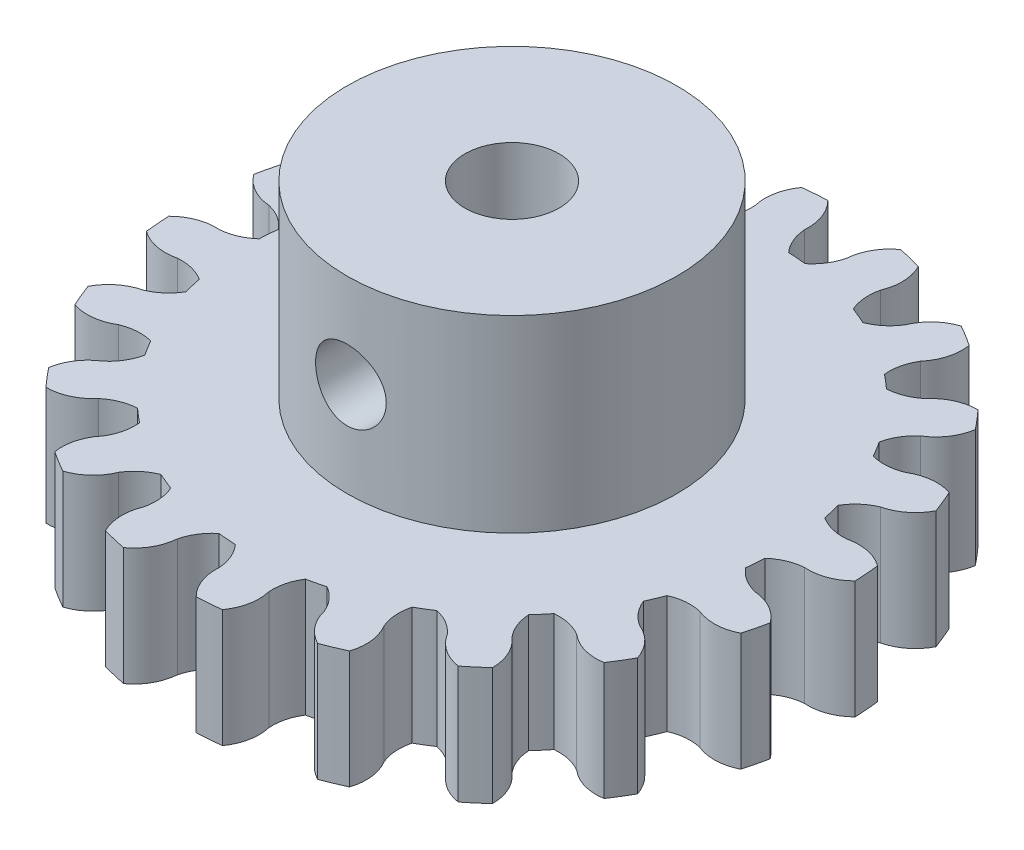
SolidWorks part; units mm, degrees
ref_plane "Front Plane" through (0, 0, 0) normal (0, 0, 1) x (1, 0, 0)
ref_plane "Top Plane" through (0, 0, 0) normal (0, 1, 0) x (1, 0, 0)
ref_plane "Right Plane" through (0, 0, 0) normal (1, 0, 0) x (0, 0, -1)
sketch "Sketch1" plane through (0, 0, 0) normal (0, 1, 0) x (1, 0, 0)
  circle A0 centre (0, 0) radius 14
  circle A1 centre (0, 0) radius 12.73
  circle A2 centre (0, 0) radius 11.25
  circle A3 centre (0, 12.73) radius 2
  circle A4 centre (1.9938, 12.5729) radius 2
  circle A5 centre (-1.9938, 12.5729) radius 2
  circle A6 centre (3.9384, 12.1054) radius 2
  dimension "D1" = 28
  dimension "D2" = 25.46
  dimension "D3" = 22.5
extrude "Boss-Extrude2" add sketch "Sketch1" along normal blind 6 contours A0
extrude "Cut-Extrude4" cut sketch "Sketch1<3>" along normal blind 14 contours A5 A4 A0 | A6 A1 A5 A4 A2 A3 | A0 A4 A1 A3 | A6 A0 A3 region at (2.1397, 0, -13.4931) region at (0, 0, -13.6617) region at (1.0446, 0, -13.2561) region at (0.9482, 0, -12.0329)
sketch "Sketch1<3>" plane through (0, 0, 0) normal (0, 1, 0) x (1, 0, 0) same geometry as "Sketch1"
pattern_circular "CirPattern2" count 20 over 360 about axis through (0, 6, 0) along (0, 1, 0) of "Cut-Extrude4"
sketch "Sketch6" plane through (0, 6, 0) normal (0, 1, 0) x (1, 0, 0)
  circle A0 centre (0, 0) radius 2
extrude "Cut-Extrude5" cut sketch "Sketch6" against normal blind 14
sketch "Sketch7" plane through (0, 0, 0) normal (0, -1, 0) x (-1, 0, 0)
  circle A0 centre (0, 0) radius 19.1841
extrude "Cut-Extrude6" cut sketch "Sketch7" against normal blind 1
sketch "Sketch8" plane through (0, 6, 0) normal (0, 1, 0) x (1, 0, 0)
  circle A0 centre (0, 0) radius 2
  circle A1 centre (0, 0) radius 7
extrude "Boss-Extrude3" add sketch "Sketch8" along normal blind 8
sketch "Sketch9" plane through (0, 0, 0) normal (0, 0, 1) x (1, 0, 0)
  line L0 (0, 14) -> (0, 10) construction
  line L1 (7, 14) -> (-7, 14) construction
  circle A0 centre (0, 10) radius 1.5
extrude "Cut-Extrude7" cut sketch "Sketch9" along normal blind 16 and the other way blind 15
